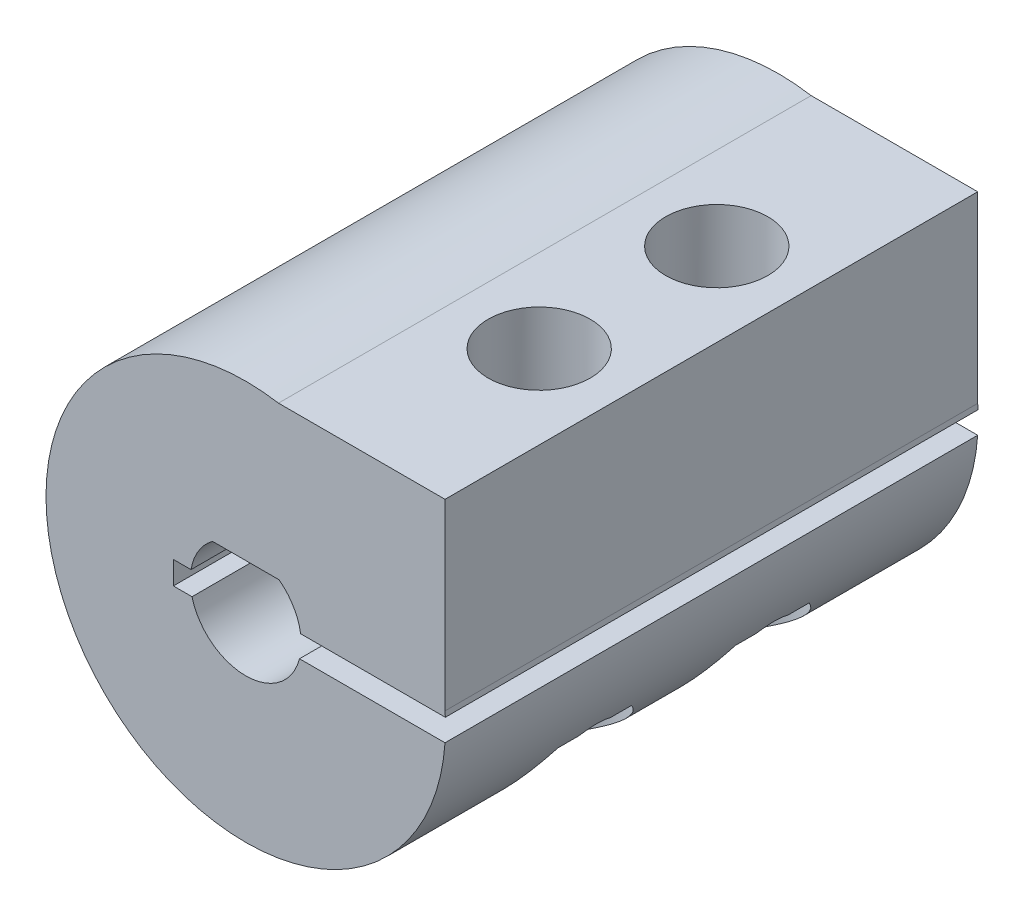
SolidWorks part; units mm, degrees
ref_plane "Front Plane" through (0, 0, 0) normal (0, 0, 1) x (1, 0, 0)
ref_plane "Top Plane" through (0, 0, 0) normal (0, 1, 0) x (1, 0, 0)
ref_plane "Right Plane" through (0, 0, 0) normal (1, 0, 0) x (0, 0, -1)
sketch "Sketch1" plane through (0, 0, 0) normal (0, 0, 1) x (1, 0, 0)
  line L1 (-2.4444, -0.6215) -> (-1.3652, -0.6215)
  line L2 (-2.4444, -0.6215) -> (-2.4444, 0.3785)
  line L3 (-2.4444, 0.3785) -> (-1.4515, 0.3785)
  line L7 (1.3652, -0.6215) -> (8.9785, -0.6215)
  line L9 (1.4515, 0.3785) -> (8.992, 0.3785)
  arc A0 (-1.3652, -0.6215) -> (1.3652, -0.6215) centre (0, 0) ccw
  arc A1 (8.992, 0.3785) -> (8.9785, -0.6215) centre (0, 0) ccw
  arc A2 (1.4515, 0.3785) -> (-1.4515, 0.3785) centre (0, 0) ccw
  dimension "D1" = 3
  dimension "D2" = 18
extrude "Boss-Extrude1" add sketch "Sketch1" along normal blind 8
sketch "Sketch14" plane through (0, 0, 8) normal (0, 0, 1) x (1, 0, 0)
  line L1 (-1.5, 2) -> (0, 2)
  line L2 (0, 2) -> (1.5, 2)
  line L3 (-2.4658, 0.4121) -> (-3.2608, 0.4121)
  line L7 (-3.2608, -0.6222) -> (-3.2608, 0.4121)
  line L12 (-2.4213, -0.6222) -> (-3.2608, -0.6222)
  arc A0 (-1.5, 2) -> (-2.4658, 0.4121) centre (0, 0) ccw
  arc A2 (-2.4213, -0.6222) -> (1.5, 2) centre (0, 0) ccw
  point P1 (-1.5, -0.0991)
  dimension "D1" = 5
sketch "Sketch3" plane through (0, 0.3785, 0) normal (0, -1, 0) x (1, 0, 0)
  line L0 (1.4515, 8) -> (8.992, 0) construction
  circle A0 centre (5.2218, 4) radius 1.95
  dimension "D1" = 3.9
extrude "Cut-Extrude1" cut sketch "Sketch3" against normal blind 8
sketch "Sketch4" plane through (0, -0.6215, 0) normal (0, 1, 0) x (1, 0, 0)
  line L4 (8.9785, 0) -> (1.3652, 0)
  line L5 (1.3652, 0) -> (1.3652, -8)
  line L6 (1.3652, -8) -> (8.9785, -8)
  line L7 (8.9785, -8) -> (8.9785, 0)
  line L8 (8.9785, 0) -> (1.3652, 0)
  line L9 (1.3652, 0) -> (1.3652, -8)
  line L10 (1.3652, -8) -> (8.9785, -8)
  line L11 (8.9785, -8) -> (8.9785, 0)
  circle A0 centre (5.2218, -4) radius 1.95 construction
  circle A1 centre (5.2218, -4) radius 1.95
  circle A2 centre (5.2218, -4) radius 1.5
  dimension "D2" = 3
  dimension "D1" = 0
extrude "Cut-Extrude2" cut sketch "Sketch4" against normal blind 8 contours A2 region at (5.2218, -0.6215, 4)
ref_plane "Plane1" through (0, -2.6215, 0) normal (0, 1, 0) x (1, 0, 0)
sketch "Sketch5" plane through (0, -2.6215, 0) normal (0, 1, 0) x (1, 0, 0)
  circle A0 centre (5.2218, -4) radius 2.6
  dimension "D1" = 5.2
extrude "Cut-Extrude3" cut sketch "Sketch5" against normal blind 8
sketch "Sketch6" plane through (0, 0, 0) normal (0, 0, -1) x (-1, 0, 0)
  line L0 (1.3652, -0.6215) -> (2.4444, -0.6215) construction
  line L1 (2.4444, -0.6215) -> (2.4444, 0.3785) construction
  line L2 (2.4444, 0.3785) -> (1.4515, 0.3785) construction
  line L3 (1.9167, -0.6215) -> (2.4444, -0.6215)
  line L4 (2.4444, -0.6215) -> (2.4444, 0.3785)
  line L5 (-8.992, 0.3785) -> (-1.4515, 0.3785)
  line L6 (1.4515, 0.3785) -> (2.4444, 0.3785)
  line L7 (2.4444, 0.3785) -> (2.4444, -0.6215)
  line L8 (2.4444, -0.6215) -> (1.3652, -0.6215)
  line L9 (-1.3652, -0.6215) -> (-8.9785, -0.6215)
  line L10 (-8.992, 0.3785) -> (-1.9791, 0.3785)
  line L14 (-1.9167, -0.6215) -> (-8.9785, -0.6215)
  line L15 (2.4444, 0.3785) -> (1.9791, 0.3785)
  arc A0 (-1.9167, -0.6215) -> (1.9167, -0.6215) centre (0, 0) ccw
  arc A1 (1.9791, 0.3785) -> (-1.9791, 0.3785) centre (0, 0) ccw
  arc A3 (-8.9785, -0.6215) -> (-8.992, 0.3785) centre (0, 0) ccw
  arc A4 (1.4515, 0.3785) -> (-1.4515, 0.3785) centre (0, 0) ccw
  arc A5 (-1.3652, -0.6215) -> (1.3652, -0.6215) centre (0, 0) ccw
  arc A6 (-8.9785, -0.6215) -> (-8.992, 0.3785) centre (0, 0) ccw
  dimension "D2" = 4.03
  dimension "D1" = 0
extrude "Boss-Extrude2" add sketch "Sketch6" along normal blind 12
mirror "Mirror1" about plane through (0, 0, 0) normal (0, 0, 1) of "Cut-Extrude2", "Cut-Extrude3", "Cut-Extrude1"
ref_plane "Plane2" through (0, 3.3785, 0) normal (0, -1, 0) x (-1, 0, 0)
sketch "Sketch7" plane through (0, 3.3785, 0) normal (0, -1, 0) x (-1, 0, 0)
  circle A0 centre (-5.2218, 4) radius 2.3
  dimension "D1" = 4.6
extrude "Cut-Extrude4" cut sketch "Sketch7" against normal blind 12 from offset 2 offset against normal yes
mirror "Mirror2" about plane through (0, 0, 0) normal (0, 0, 1) of "Cut-Extrude4"
sketch "Sketch9" plane through (0, 0.3785, 0) normal (0, -1, 0) x (1, 0, 0)
  line L1 (1.465, 0) -> (8.9785, 0)
  line L2 (1.465, 0) -> (1.465, 8)
  line L3 (1.465, 8) -> (8.9785, 8)
  line L4 (8.9785, 0) -> (8.9785, 8)
  line L5 (1.465, 0) -> (8.9785, 8) construction
  line L6 (1.465, 8) -> (8.9785, 0) construction
  arc A0 (7.2161, 5.1457) -> (7.2161, 2.8543) centre (5.2218, 4) ccw construction
  circle A1 centre (5.2218, 4) radius 2.3
  point P0 (5.2218, 4)
extrude "Boss-Extrude3" add sketch "Sketch9" against normal blind 8.5
mirror "Mirror3" about plane through (0, 0, 0) normal (0, 0, 1) of "Boss-Extrude3", "Mirror2"
sketch "Sketch10" plane through (0, -2.6215, 0) normal (0, 1, 0) x (1, 0, 0)
  circle A0 centre (5.2218, 4) radius 3
  circle A1 centre (5.2218, -4) radius 3
  dimension "D1" = 6
  dimension "D2" = 6
extrude "Cut-Extrude7" cut sketch "Sketch10" against normal blind 8.5 from offset 2 offset against normal yes
ref_plane "Plane3" through (0, 0, -4) normal (0, 0, -1) x (-1, 0, 0)
sketch "Sketch13" plane through (0, 0, 8) normal (0, 0, 1) x (1, 0, 0)
  line L7 (1.4515, 0.3785) -> (8.992, 0.3785)
  line L8 (8.9785, 0.6215) -> (8.9785, 8.8785)
  line L9 (8.9785, 8.8785) -> (1.4741, 8.8785)
  line L10 (8.9785, -0.6215) -> (1.3652, -0.6215)
  line L11 (-1.3652, -0.6215) -> (-2.4444, -0.6215)
  line L12 (-2.4444, -0.6215) -> (-2.4444, 0.3785)
  line L13 (-2.4444, 0.3785) -> (-1.4515, 0.3785)
  line L14 (1.4515, 0.3785) -> (8.992, 0.3785)
  line L15 (8.9785, 0.6215) -> (8.9785, 8.8785)
  line L16 (8.9785, 8.8785) -> (1.4741, 8.8785)
  line L17 (8.9785, -0.6215) -> (1.3652, -0.6215)
  line L18 (-1.3652, -0.6215) -> (-2.4444, -0.6215)
  line L19 (-2.4444, -0.6215) -> (-2.4444, 0.3785)
  line L20 (-2.4444, 0.3785) -> (-1.4515, 0.3785)
  arc A4 (8.992, 0.3785) -> (8.9785, 0.6215) centre (0, 0) ccw
  arc A5 (1.4741, 8.8785) -> (8.9785, -0.6215) centre (0, 0) ccw
  arc A6 (-1.3652, -0.6215) -> (1.3652, -0.6215) centre (0, 0) ccw
  arc A7 (1.4515, 0.3785) -> (-1.4515, 0.3785) centre (0, 0) ccw
  arc A8 (8.992, 0.3785) -> (8.9785, 0.6215) centre (0, 0) ccw
  arc A9 (1.4741, 8.8785) -> (8.9785, -0.6215) centre (0, 0) ccw
  arc A10 (-1.3652, -0.6215) -> (1.3652, -0.6215) centre (0, 0) ccw
  arc A11 (1.4515, 0.3785) -> (-1.4515, 0.3785) centre (0, 0) ccw
  dimension "D1" = 0
extrude "Boss-Extrude6" add sketch "Sketch13" along normal blind 4
extrude "Cut-Extrude8" cut sketch "Sketch14" against normal up to surface (8 mm away) up to face at (0, -1.1895, 0)
extrude "Cut-Extrude9" cut sketch "Sketch14<2>" along normal up to surface (4 mm away) up to face at (1.8386, 0.722, 12)
sketch "Sketch14<2>" plane through (0, 0, 8) normal (0, 0, 1) x (1, 0, 0) same geometry as "Sketch14"
sketch "Sketch15" plane through (0, 0, -8) normal (0, 0, -1) x (-1, 0, 0)
  line L2 (-8.9785, 8.8785) -> (-8.9785, 0.6215)
  line L3 (-1.4741, 8.8785) -> (-8.9785, 8.8785)
  line L4 (-8.9785, 8.8785) -> (-8.9785, 0.6215)
  line L5 (-1.4741, 8.8785) -> (-8.9785, 8.8785)
  arc A1 (-1.4741, 8.8785) -> (-8.9785, 0.6215) centre (0, 0) ccw
  arc A2 (-1.4741, 8.8785) -> (-8.9785, 0.6215) centre (0, 0) ccw
  dimension "D1" = 0
extrude "Boss-Extrude7" add sketch "Sketch15" along normal up to surface (4 mm away) up to face at (-0.6128, -0.0607, -12)
